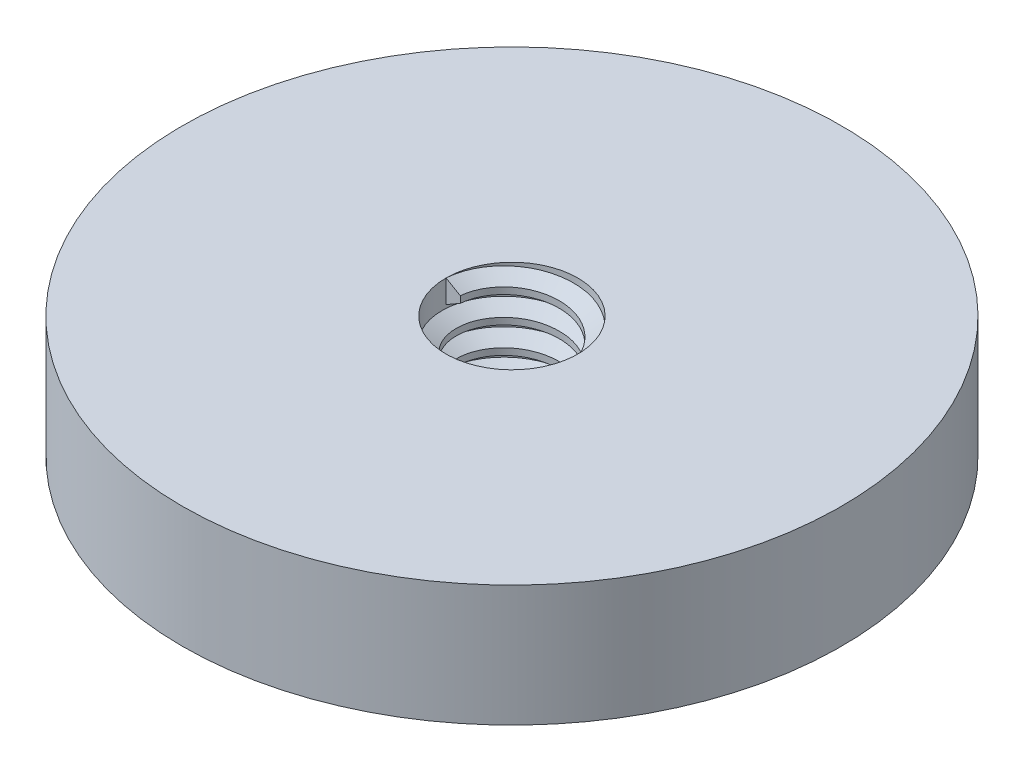
SolidWorks part; units mm, degrees
material "AISI 1020"
ref_plane "Front Plane" through (0, 0, 0) normal (0, 0, 1) x (1, 0, 0)
ref_plane "Top Plane" through (0, 0, 0) normal (0, 1, 0) x (1, 0, 0)
ref_plane "Right Plane" through (0, 0, 0) normal (1, 0, 0) x (0, 0, -1)
sketch "Sketch1" plane through (0, 0, 0) normal (0, 1, 0) x (1, 0, 0)
  circle A0 centre (0, 0) radius 15.875
  circle A1 centre (0, 0) radius 3.175
  dimension "D1" = 31.75
  dimension "D2" = 6.35
extrude "Boss-Extrude1" add sketch "Sketch1" along normal blind 5.842
thread "Thread1" pitch 1.27 method extrude profile "Thread Profile1" start angle 0, offset 0, length 0, pitch 1.27, diameter 6.35
ref_plane "Plane1" through (-3.175, 5.842, 0) normal (0, 0, 1) x (-1, 0, 0)
sketch "Thread Profile1" plane through (-3.175, 5.842, 0) normal (0, 0, 1) x (-1, 0, 0)
  line L0 (0, 0) -> (0, 1.27) construction
  line L11 (0, 0) -> (0, 1.1112)
  line L12 (0, 1.1112) -> (-0.6874, 0.7144)
  line L13 (-0.6874, 0.7144) -> (-0.6874, 0.3969)
  line L15 (-0.6874, 0.3969) -> (0, 0)
  line L17 (-0.6874, 0.5556) -> (0, 0.5556) construction
  point P2 (0, 0)
  dimension "Pitch" = 1.27
  dimension "Profile_Angle" = 60
  dimension "Profile_Land" = 0.3175
  dimension "Profile_Height" = 0.6874
